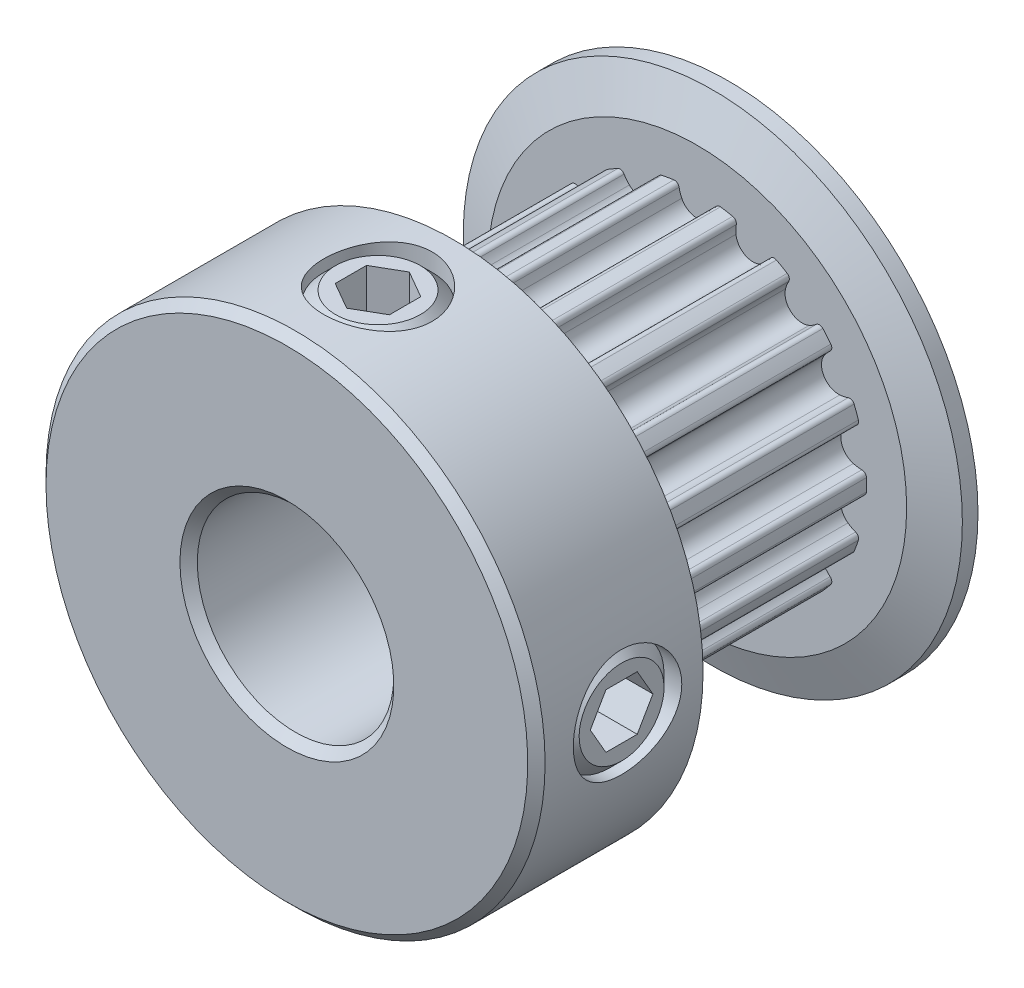
SolidWorks part; units mm, degrees
material "6061-T6 (SS)"
ref_plane "Front Plane" through (0, 0, 0) normal (0, 0, 1) x (1, 0, 0)
ref_plane "Top Plane" through (0, 0, 0) normal (0, 1, 0) x (1, 0, 0)
ref_plane "Right Plane" through (0, 0, 0) normal (1, 0, 0) x (0, 0, -1)
sketch "Sketch1" plane through (0, 0, 0) normal (0, 0, 1) x (1, 0, 0)
  line L1 (-1.7295, 4.7235) -> (1.7295, 4.7235) construction
  line L4 (0, 0) -> (0, 4.7235) construction
  line L5 (0, 4.7235) -> (0, 10.7878) construction
  line L6 (0, 5.7275) -> (1.9693, 5.3783) construction
  line L7 (1.9693, 5.3783) -> (2.6241, 5.1385) construction
  line L8 (1.9693, 5.3783) -> (1.7295, 4.7235) construction
  line L9 (-1.9693, 5.3783) -> (-1.7295, 4.7235) construction
  line L10 (-1.8819, 5.1398) -> (-2.9528, 8.0645)
  line L11 (-2.9528, 8.0645) -> (2.9528, 8.0645)
  line L12 (2.9528, 8.0645) -> (1.8819, 5.1398)
  circle A0 centre (0, 0) radius 5.7275 construction
  circle A1 centre (0, 0) radius 8.0645 construction
  circle A2 centre (0, 0) radius 5.4735 construction
  arc A3 (-0.4989, 5.0353) -> (0.4989, 5.0353) centre (0, 5.2785) ccw
  arc A4 (-0.4989, 5.0353) -> (-0.5847, 5.2991) centre (0.4, 5.4735) cw
  arc A5 (-1.8819, 5.1398) -> (-0.753, 5.4215) centre (0, 0) cw
  arc A6 (-0.5847, 5.2991) -> (-0.753, 5.4215) centre (-0.7324, 5.2729) ccw
  arc A7 (1.8819, 5.1398) -> (0.753, 5.4215) centre (0, 0) ccw
  arc A8 (0.5847, 5.2991) -> (0.753, 5.4215) centre (0.7324, 5.2729) cw
  arc A9 (0.4989, 5.0353) -> (0.5847, 5.2991) centre (-0.4, 5.4735) ccw
  point P6 (0, 20.9083)
  point P11 (0, 5.7275)
  point P13 (0, 8.0645)
  point P14 (0, 5.4735)
  dimension "D1" = 10.1206
  dimension "D2" = 5.0603
sketch "Sketch2" plane through (0, 0, 0) normal (1, 0, 0) x (0, 0, -1)
  line L0 (-7.135, 3.175) -> (7.135, 3.175)
  line L1 (-7.135, 3.175) -> (-7.135, 8.0645)
  line L2 (-1.75, 8.0645) -> (-7.135, 8.0645)
  line L3 (-2.255, 3.175) -> (-2.255, 8.0645) construction
  line L4 (-2.255, 8.0645) -> (-1.245, 8.0645) construction
  line L5 (-1.245, 8.0645) -> (-1.245, 5.4735) construction
  line L6 (-1.245, 5.4735) -> (6.125, 5.4735)
  line L7 (6.125, 5.4735) -> (6.125, 8.0645) construction
  line L8 (6.125, 8.0645) -> (7.135, 8.0645) construction
  line L9 (7.135, 8.0645) -> (7.135, 3.175)
  line L10 (-7.135, 0) -> (7.135, 0) construction
  line L11 (6.63, 8.0645) -> (6.125, 6.769)
  line L12 (-1.245, 6.769) -> (-1.75, 8.0645)
  line L14 (-1.245, 6.769) -> (-1.245, 5.4735)
  line L15 (6.125, 5.4735) -> (6.125, 6.769)
  line L16 (6.63, 8.0645) -> (7.135, 8.0645)
  arc A0 (-1.245, 6.769) -> (-1.75, 8.0645) centre (-3.1592, 6.769) ccw construction
  arc A1 (6.125, 6.769) -> (6.63, 8.0645) centre (8.0392, 6.769) cw construction
  point P12 (-1.245, 6.769)
  point P14 (-1.75, 8.0645)
  point P20 (6.125, 6.769)
  point P21 (6.63, 8.0645)
  point P25 (6.125, 0)
  point P26 (-1.245, 0)
  dimension "OA" = 14.27
  dimension "Bore" = 6.35
  dimension "Outside Width" = 8.38
  dimension "Inside Width" = 7.37
revolve "Revolve1" add sketch "Sketch2" angle 360 mid plane about L10
sketch "Sketch3" plane through (0, 0, 0) normal (0, 0, 1) x (1, 0, 0)
  line L6 (2.9528, 8.0645) -> (-2.9528, 8.0645)
  line L7 (1.8819, 5.1398) -> (2.9528, 8.0645)
  line L8 (-2.9528, 8.0645) -> (-1.8819, 5.1398)
  line L9 (2.9528, 8.0645) -> (-2.9528, 8.0645)
  line L10 (1.8819, 5.1398) -> (2.9528, 8.0645)
  line L11 (-2.9528, 8.0645) -> (-1.8819, 5.1398)
  arc A8 (1.8819, 5.1398) -> (0.753, 5.4215) centre (0, 0) ccw
  arc A9 (0.753, 5.4215) -> (0.5847, 5.2991) centre (0.7324, 5.2729) ccw
  arc A10 (0.4989, 5.0353) -> (0.5847, 5.2991) centre (-0.4, 5.4735) ccw
  arc A11 (-0.4989, 5.0353) -> (0.4989, 5.0353) centre (0, 5.2785) ccw
  arc A12 (-0.5847, 5.2991) -> (-0.4989, 5.0353) centre (0.4, 5.4735) ccw
  arc A13 (-0.5847, 5.2991) -> (-0.753, 5.4215) centre (-0.7324, 5.2729) ccw
  arc A14 (-0.753, 5.4215) -> (-1.8819, 5.1398) centre (0, 0) ccw
  arc A15 (1.8819, 5.1398) -> (0.753, 5.4215) centre (0, 0) ccw
  arc A16 (0.753, 5.4215) -> (0.5847, 5.2991) centre (0.7324, 5.2729) ccw
  arc A17 (0.4989, 5.0353) -> (0.5847, 5.2991) centre (-0.4, 5.4735) ccw
  arc A18 (-0.4989, 5.0353) -> (0.4989, 5.0353) centre (0, 5.2785) ccw
  arc A19 (-0.5847, 5.2991) -> (-0.4989, 5.0353) centre (0.4, 5.4735) ccw
  arc A20 (-0.5847, 5.2991) -> (-0.753, 5.4215) centre (-0.7324, 5.2729) ccw
  arc A21 (-0.753, 5.4215) -> (-1.8819, 5.1398) centre (0, 0) ccw
  dimension "D1" = 0
extrude "Cut-Extrude1" cut sketch "Sketch3" against normal up to vertex (6.125 mm away) from vertex up to point (0, 5.4735, -6.125) starting at point (0, 5.4735, 1.245)
pattern_circular "CirPattern1" count 18 over 360 about axis through (0, 0, 7.135) along (0, 0, 1) of "Cut-Extrude1"
sketch "Sketch4" plane through (0, 0, 0) normal (1, 0, 0) x (0, -1, 0)
  line L0 (0, -1.245) -> (0, -7.135) construction
  line L1 (-3.175, -7.135) -> (3.175, -7.135) construction
  line L2 (6.769, -1.245) -> (-6.769, -1.245) construction
  circle A0 centre (0, -4.19) radius 1.7526
extrude "Cut-Extrude2" cut sketch "Sketch4" along normal through all
ref_plane "Plane1" through (0, 0, 4.19) normal (0, 0, 1) x (1, 0, 0)
sketch "Sketch5" plane through (0, 0, 4.19) normal (0, 0, 1) x (1, 0, 0)
  line L0 (0, 0) -> (0, 8.0645) construction
  line L1 (3.175, -1.3716) -> (3.175, 0)
  line L2 (3.556, -1.7526) -> (7.4908, -1.7526)
  line L3 (3.175, 0) -> (8.0645, 0) construction
  line L4 (3.175, 0) -> (7.8718, 0)
  line L5 (7.8718, 0) -> (7.8718, -1.3716)
  line L6 (3.556, -1.7526) -> (3.175, -1.3716)
  line L7 (7.8718, -1.3716) -> (7.4908, -1.7526)
  circle A0 centre (0, 0) radius 8.0645 construction
  circle A1 centre (0, 0) radius 3.175 construction
  point P2 (3.175, -1.7526)
  point P11 (7.8718, -1.7526)
revolve "Revolve2" add sketch "Sketch5" angle 360 mid plane about L4
sketch "Sketch6" plane through (7.8718, 5.3841, 0) normal (-1, 0, 0) x (0, -1, 0)
  line L1 (5.3841, 5.2019) -> (4.5078, 4.6959)
  line L2 (4.5078, 4.6959) -> (4.5078, 3.6841)
  line L3 (4.5078, 3.6841) -> (5.3841, 3.1781)
  line L4 (5.3841, 3.1781) -> (6.2604, 3.6841)
  line L5 (6.2604, 3.6841) -> (6.2604, 4.6959)
  line L6 (6.2604, 4.6959) -> (5.3841, 5.2019)
  circle A0 centre (5.3841, 4.19) radius 0.8763 construction
  dimension "D1" = 1.7526
extrude "Cut-Extrude3" cut sketch "Sketch6" along normal blind 1.3144
pattern_circular "CirPattern3" count 2 over 90 about axis through (0, 0, 7.135) along (0, 0, 1) of "Cut-Extrude2", "Revolve2", "Cut-Extrude3"
chamfer "Chamfer1" distance 0.2807 angle 45 2 edges at (3.175, 0, 7.135) (8.0645, 0, 7.135)
ref_axis "Center Axis 1" through (0, 0, -7.135) along (0, 0, 1)
ref_plane "Contact Plane 1" through (0, 0, 7.135) normal (0, 0, 1) x (1, 0, 0)
ref_plane "Contact Plane 2" through (0, 0, -7.135) normal (0, 0, -1) x (-1, 0, 0)
equation "\"D2@Sketch1\"= \"D1@Sketch1\" / 2"
equation "\"D1@Sketch6\" = \"Set Screw@Sketch4\" / 2"
equation "\"D1@Cut-Extrude3\" = \"D1@Sketch6\"*.75"
